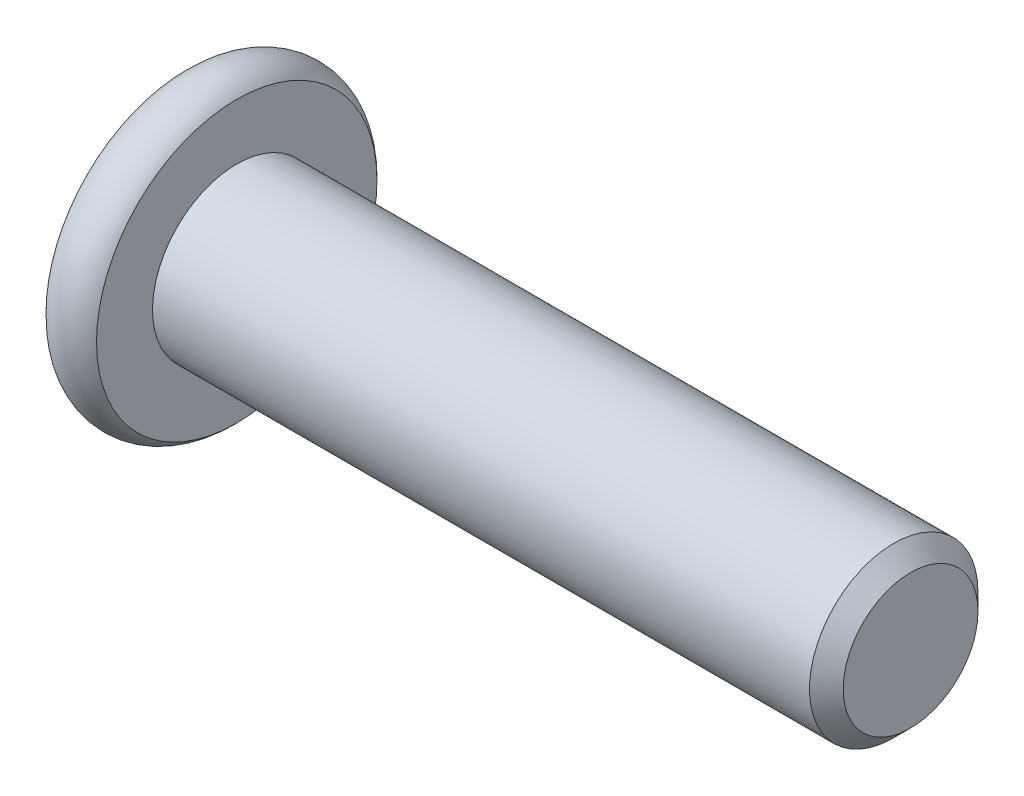
SolidWorks part; units mm, degrees
material "Plain Carbon Steel"
ref_plane "Front Plane" through (0, 0, 0) normal (0, 0, 1) x (1, 0, 0)
ref_plane "Top Plane" through (0, 0, 0) normal (0, 1, 0) x (1, 0, 0)
ref_plane "Right Plane" through (0, 0, 0) normal (1, 0, 0) x (0, 0, -1)
other "M5 x 15"
sketch "Sketch2" plane through (0, 0, 0) normal (1, 0, 0) x (0, 0, -1)
  circle A0 centre (0, 0) radius 2.5
  dimension "D1" = 5
extrude "Boss-Extrude1" add sketch "Sketch2" against normal blind 20
chamfer "Chamfer1" distance 0.5 angle 45 1 edges at (0, 0, -2.5)
sketch "Sketch6" plane through (0, 0, 0) normal (0, 0, 1) x (1, 0, 0)
  line L0 (-21.5, 0) -> (-21.5, 4.1614)
  line L1 (-21.5, 0) -> (-20, 0)
  line L2 (-20.75, 0) -> (-20.75, 3.5) construction
  line L6 (-20, 4.1614) -> (-20, 0)
  line L8 (-20, 0) -> (-14.6471, 0) construction
  line L10 (-20, 2.5) -> (-20, -2.5) construction
  arc A0 (-21.5, 4.1614) -> (-20, 4.1614) centre (-20.75, 3.5) cw
  dimension "D3" = 1
  dimension "D1" = 1.5
  dimension "D2" = 9
revolve "Revolve1" add sketch "Sketch6" angle 360 about L8
sketch "Sketch7" plane through (-21.5, 0, 0) normal (-1, 0, 0) x (0, 0, 1)
  line L1 (0, 1.7321) -> (-1.5, 0.866)
  line L2 (-1.5, 0.866) -> (-1.5, -0.866)
  line L3 (-1.5, -0.866) -> (0, -1.7321)
  line L4 (0, -1.7321) -> (1.5, -0.866)
  line L5 (1.5, -0.866) -> (1.5, 0.866)
  line L6 (1.5, 0.866) -> (0, 1.7321)
  circle A0 centre (0, 0) radius 1.5 construction
  dimension "D1" = 3
extrude "Cut-Extrude1" cut sketch "Sketch7" against normal blind 2.3
sketch "Sketch8" plane through (-21.5, 0, 0) normal (-1, 0, 0) x (0, 0, 1)
  circle A0 centre (0, 0) radius 1.7821
  dimension "D1" = 0.05
extrude "Cut-Extrude2" cut sketch "Sketch8" against normal blind 1 draft 45
